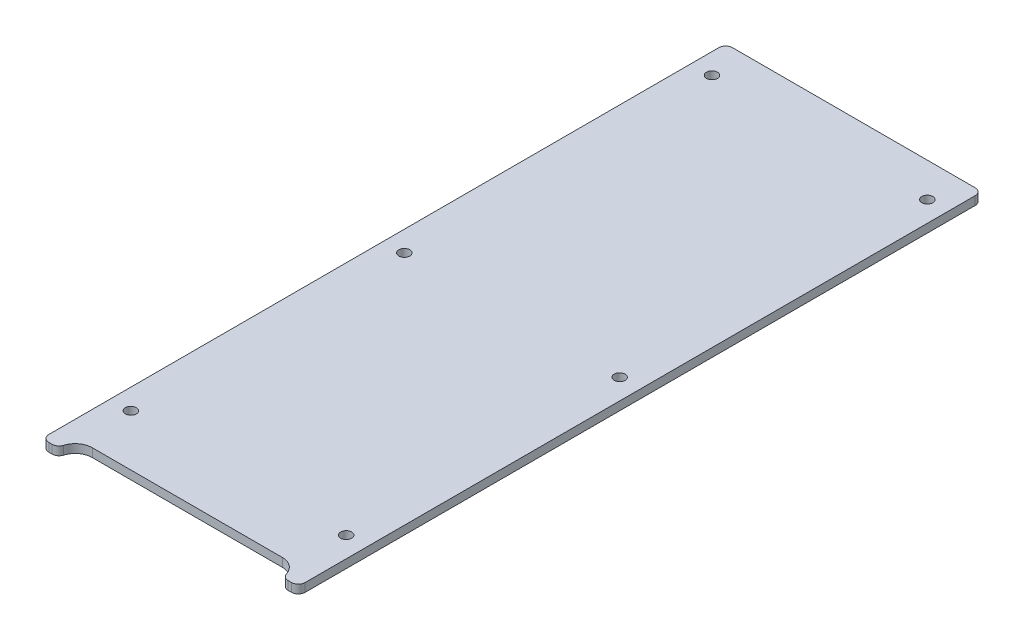
SolidWorks part; units mm, degrees
ref_plane "Front Plane" through (0, 0, 0) normal (0, 0, 1) x (1, 0, 0)
ref_plane "Top Plane" through (0, 0, 0) normal (0, 1, 0) x (1, 0, 0)
ref_plane "Right Plane" through (0, 0, 0) normal (1, 0, 0) x (0, 0, -1)
sketch "Sketch1" plane through (0, 0, 0) normal (0, 1, 0) x (1, 0, 0)
  line L0 (-39.9997, 0) -> (-39.9997, 114.3) construction
  line L1 (-47.625, 127) -> (47.625, 127)
  line L2 (-47.625, 127) -> (-47.625, -127)
  line L3 (-47.625, -127) -> (47.625, -127)
  line L4 (47.625, 127) -> (47.625, -127)
  line L5 (-47.625, 127) -> (47.625, -127) construction
  line L6 (-47.625, -127) -> (47.625, 127) construction
  line L7 (0, 0) -> (0, 127) construction
  line L8 (-39.9997, 0) -> (-39.9997, -101.6) construction
  line L9 (-39.9997, 0) -> (0, 0) construction
  line L10 (-41.275, -127) -> (-41.275, -120.65)
  line L11 (-41.275, -120.65) -> (41.275, -120.65)
  line L12 (41.275, -120.65) -> (41.275, -127)
  circle A0 centre (-39.9997, 114.3) radius 2.032
  circle A1 centre (-39.9997, 0) radius 2.032
  circle A2 centre (-39.9997, -101.6) radius 2.032
  circle A3 centre (39.9997, -101.6) radius 2.032
  circle A4 centre (39.9997, 0) radius 2.032
  circle A5 centre (39.9997, 114.3) radius 2.032
  point P0 (0, 0)
  dimension "D4" = 4.064
  dimension "D1" = 95.25
  dimension "D2" = 254
  dimension "D3" = 7.6253
  dimension "D5" = 12.7
  dimension "D6" = 25.4
  dimension "D7" = 6.35
  dimension "D8" = 6.35
  dimension "D9" = 6.35
extrude "Boss-Extrude1" add sketch "Sketch1" along normal blind 3.175 contours L4 L1 L2 L3 A4 A0 A1 A2 A3 A5 region at (0, 0, -2.7374)
fillet "Fillet1" radius 2.54 4 edges at (-47.625, 1.5875, -127) (47.625, 1.5875, -127) (47.625, 1.5875, 127) (-47.625, 1.5875, 127)
fillet "Fillet2" radius 2.54 2 edges at (41.275, 1.5875, 127) (-41.275, 1.5875, 127)
fillet "Fillet3" radius 6.35 2 edges at (41.275, 1.5875, 120.65) (-41.275, 1.5875, 120.65)
